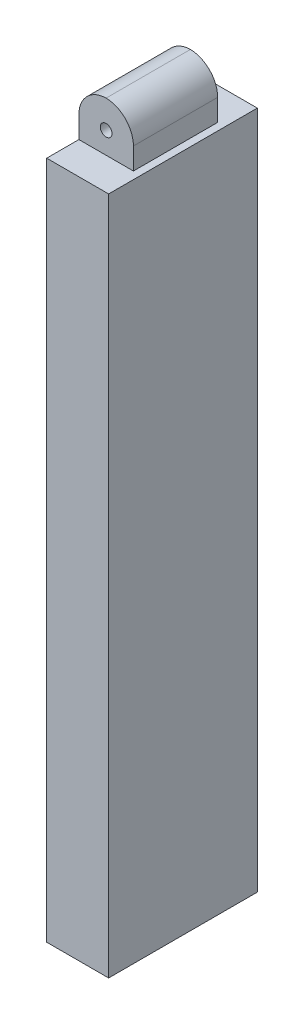
SolidWorks part; units mm, degrees
ref_plane "Front Plane" through (0, 0, 0) normal (1, 0, 0) x (0, 1, 0)
ref_plane "Top Plane" through (0, 0, 0) normal (0, 0, 1) x (0, 1, 0)
ref_plane "Right Plane" through (0, 0, 0) normal (0, 1, 0) x (-1, 0, 0)
sketch "Sketch1" plane through (0, 0, 0) normal (1, 0, 0) x (0, 1, 0)
  line L1 (-54.8, -12) -> (54.8, -12)
  line L2 (-54.8, -12) -> (-54.8, 12)
  line L3 (-54.8, 12) -> (54.8, 12)
  line L4 (54.8, -12) -> (54.8, 12)
  line L5 (-54.8, -12) -> (54.8, 12) construction
  line L6 (-54.8, 12) -> (54.8, -12) construction
  line L7 (44.8, 10) -> (-54.8, 10)
  line L8 (44.8, 10) -> (44.8, -10)
  line L9 (44.8, -10) -> (-54.8, -10)
  line L10 (-54.8, 10) -> (-54.8, -10)
  point P0 (0, 0)
  dimension "D1" = 24
  dimension "D2" = 109.6
  dimension "D3" = 2
  dimension "D4" = 2
  dimension "D5" = 10
extrude "Boss-Extrude1" add sketch "Sketch1" along normal blind 10 contours L3 L4 L1 L2
sketch "Sketch3" plane through (0, 54.8, 0) normal (0, 1, 0) x (-1, 0, 0)
  line L1 (-8.8, 6.8) -> (0, 6.8)
  line L2 (-8.8, 6.8) -> (-8.8, -6.8)
  line L3 (-8.8, -6.8) -> (0, -6.8)
  line L4 (0, 6.8) -> (0, -6.8)
  line L5 (0, -12) -> (0, 12) construction
  line L6 (-10, -12) -> (0, -12) construction
  line L7 (-10, 12) -> (0, 12) construction
  line L9 (-10, -12) -> (-10, 12) construction
  dimension "D1" = 5.2
  dimension "D2" = 5.2
  dimension "D3" = 1.2
  dimension "D4" = 13.6
extrude "Boss-Extrude2" add sketch "Sketch3" along normal blind 8
fillet "Fillet1" radius 4.5 2 edges at (0, 62.8, 0) (8.8, 62.8, 0)
sketch "Sketch4" plane through (0, 0, 6.8) normal (0, 0, 1) x (1, 0, 0)
  line L0 (0, 58.3) -> (8.8, 58.3) construction
  circle A1 centre (4.4, 58.3) radius 0.95
  dimension "D1" = 1.9
extrude "Cut-Extrude1" cut sketch "Sketch4" against normal through all
